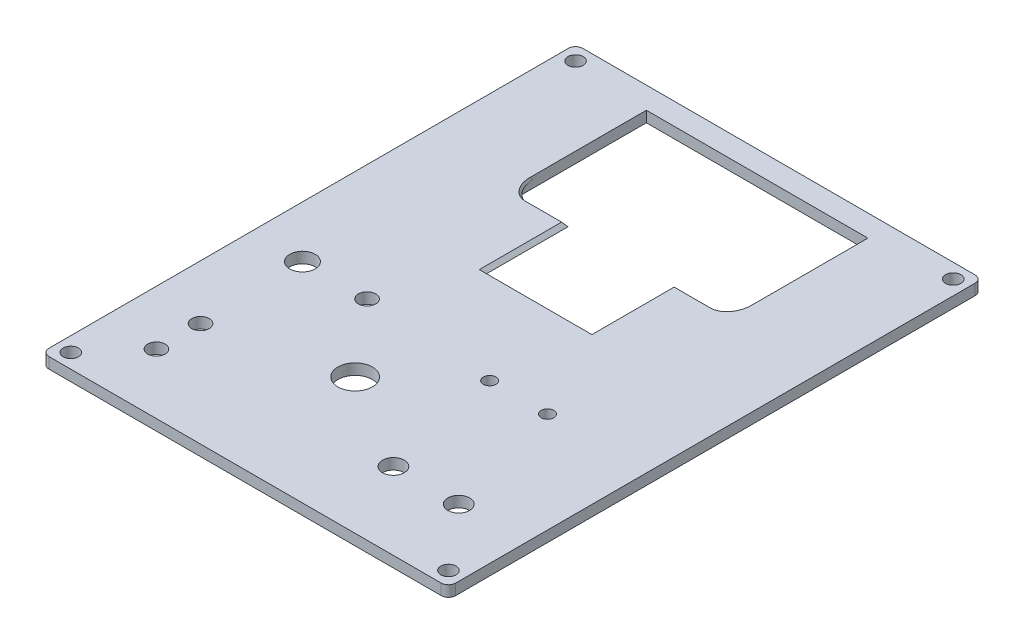
SolidWorks part; units mm, degrees
ref_plane "Front Plane" through (0, 0, 0) normal (0, 0, 1) x (1, 0, 0)
ref_plane "Top Plane" through (0, 0, 0) normal (0, 1, 0) x (1, 0, 0)
ref_plane "Right Plane" through (0, 0, 0) normal (1, 0, 0) x (0, 0, -1)
sketch "Sketch1" plane through (0, 0, 0) normal (0, 1, 0) x (1, 0, 0)
  line L1 (-56, 73.5) -> (56, 73.5)
  line L2 (-56, 73.5) -> (-56, -73.5)
  line L3 (-56, -73.5) -> (56, -73.5)
  line L4 (56, 73.5) -> (56, -73.5)
  line L5 (-56, 73.5) -> (56, -73.5) construction
  line L6 (-56, -73.5) -> (56, 73.5) construction
  point P0 (0, 0)
  dimension "D1" = 112
  dimension "D2" = 147
extrude "Boss-Extrude1" add sketch "Sketch1" along normal blind 3
ref_plane "Plane1" through (0, 2, 0) normal (0, 1, 0) x (1, 0, 0)
sketch "Sketch2" plane through (0, 3, 0) normal (0, 1, 0) x (1, 0, 0)
  line L0 (56, 73.5) -> (-56, 73.5) construction
  line L1 (-30.5, 67.5) -> (30.5, 67.5)
  line L2 (-30.5, 67.5) -> (-30.5, 6.5)
  line L3 (-30.5, 6.5) -> (30.5, 6.5)
  line L4 (30.5, 67.5) -> (30.5, 6.5)
  line L5 (-30.5, 67.5) -> (30.5, 6.5) construction
  line L6 (-30.5, 6.5) -> (30.5, 67.5) construction
  point P0 (0, 37)
  dimension "D1" = 61
  dimension "D2" = 61
  dimension "D3" = 6
extrude "Boss-Extrude2" add sketch "Sketch2" against normal blind 3
extrude "Cut-Extrude1" cut sketch "Sketch2<2>" against normal through all
sketch "Sketch2<2>" plane through (0, 3, 0) normal (0, 1, 0) x (1, 0, 0) same geometry as "Sketch2"
sketch "Sketch3" plane through (0, 3, 0) normal (0, 1, 0) x (1, 0, 0)
  line L0 (-30.5, 6.5) -> (30.5, 6.5) construction
  line L1 (-50.005, -5) -> (50.005, -5)
  line L2 (-50.005, -5) -> (-50.005, -65.01)
  line L3 (-50.005, -65.01) -> (50.005, -65.01)
  line L4 (50.005, -5) -> (50.005, -65.01)
  line L5 (-50.005, -5) -> (50.005, -65.01) construction
  line L6 (-50.005, -65.01) -> (50.005, -5) construction
  circle A1 centre (12.415, -18.57) radius 1.75
  circle A3 centre (28.345, -18.57) radius 1.75
  circle A4 centre (-41.0102, -44.7633) radius 2.4
  circle A5 centre (-41.0102, -56.9073) radius 2.4
  circle A6 centre (-23.9665, -15.9471) radius 2.4
  circle A9 centre (-7, -36.1964) radius 4.75
  circle A10 centre (19.6128, -52.279) radius 3
  circle A11 centre (37.6128, -52.279) radius 3
  circle A12 centre (-41.7535, -15.9471) radius 3.5
  point P0 (0, -35.005)
  dimension "D6" = 9.5
  dimension "D7" = 3.5
  dimension "D11" = 21.66
  dimension "D10" = 3.5
  dimension "D12" = 4.8
  dimension "D13" = 4.8
  dimension "D14" = 4.8
  dimension "D17" = 6
  dimension "D18" = 6
  dimension "D15" = 7
  dimension "D1" = 11.5
  dimension "D2" = 60.01
  dimension "D3" = 100.01
  dimension "D4" = 100.01
  dimension "D5" = 60.01
  dimension "D8" = 13.57
  dimension "D9" = 37.59
  dimension "D16" = 7
  dimension "D19" = 18
extrude "Cut-Extrude2" cut sketch "Sketch3" against normal blind 10 contours A9 | A6 | A1 | A3 | A4 | A5 | A12 | A10 | A11 region at (12.415, 3, 18.57) region at (28.345, 3, 18.57) region at (-23.9665, 3, 15.9471) region at (-7, 3, 36.1964)
sketch "Sketch4" plane through (0, 3, 0) normal (0, 1, 0) x (1, 0, 0)
  line L0 (-56, 73.5) -> (-56, -73.5) construction
  line L1 (-56, -73.5) -> (56, -73.5) construction
  circle A0 centre (-52, -69.5) radius 2.1
  dimension "D1" = 4.2
  dimension "D2" = 4
  dimension "D3" = 4
extrude "Cut-Extrude3" cut sketch "Sketch4" against normal blind 5
mirror "Mirror1" about plane through (0, 0, 0) normal (1, 0, 0) of "Cut-Extrude3"
mirror "Mirror2" about plane through (0, 0, 0) normal (0, 0, 1) of "Mirror1"
fillet "Fillet1" radius 2 4 edges at (-56, 1.5, 73.5) (-56, 1.5, -73.5) (56, 1.5, -73.5) (56, 1.5, 73.5)
sketch "Sketch5" plane through (0, 2, 0) normal (0, 1, 0) x (1, 0, 0)
  line L0 (-30.5, 67.5) -> (-30.5, 6.5) construction
  line L2 (-47.5201, -0.4184) -> (-47.5201, 31.5)
  line L5 (-47.5201, 31.5) -> (-10.5, 31.5)
  line L6 (-10.5, 31.5) -> (-10.5, -0.4184)
  line L7 (-10.5, -0.4184) -> (-47.5201, -0.4184)
  line L8 (-30.5, 6.5) -> (30.5, 6.5) construction
  dimension "D1" = 25
  dimension "D2" = 20
extrude "Boss-Extrude4" add sketch "Sketch5" along normal blind 1
chamfer "Chamfer1" distance 5 angle 45 1 edges at (-10.5, 3, -19)
chamfer "Chamfer4" distance 3 angle 38 1 edges at (-23, 3, -31.5) first distance on face at (-22.75, 2.5, -31.5)
mirror "Mirror9" about plane through (0, 0, 0) normal (1, 0, 0) of "Chamfer1", "Chamfer4", "Boss-Extrude4"
fillet "Fillet2" radius 5 2 edges at (30.5, 2.5, -29.5468) (-30.5, 2.5, -29.5468)
